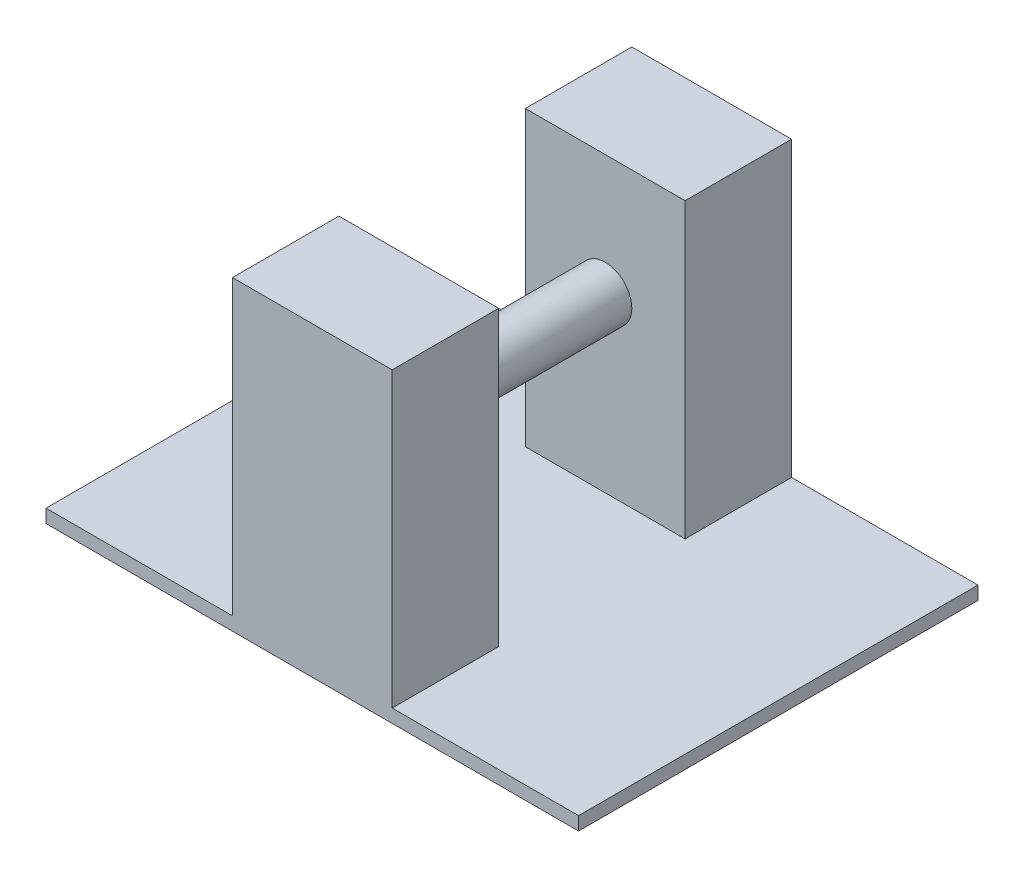
SolidWorks part; units mm, degrees
ref_plane "Front Plane" through (0, 0, 0) normal (0, 0, 1) x (1, 0, 0)
ref_plane "Top Plane" through (0, 0, 0) normal (0, 1, 0) x (1, 0, 0)
ref_plane "Right Plane" through (0, 0, 0) normal (1, 0, 0) x (0, 0, -1)
sketch "Sketch2" plane through (0, 0, 0) normal (0, 1, 0) x (1, 0, 0)
  line L1 (-127, -95.25) -> (127, -95.25)
  line L2 (-127, -95.25) -> (-127, 95.25)
  line L3 (-127, 95.25) -> (127, 95.25)
  line L4 (127, -95.25) -> (127, 95.25)
  line L5 (-127, -95.25) -> (127, 95.25) construction
  line L6 (-127, 95.25) -> (127, -95.25) construction
  point P0 (0, 0)
  dimension "D1" = 190.5
  dimension "D2" = 254
extrude "Boss-Extrude2" add sketch "Sketch2" along normal blind 6.35
sketch "Sketch4" plane through (0, 6.35, 0) normal (0, 1, 0) x (1, 0, 0)
  line L0 (-127, -95.25) -> (0, -95.25) construction
  line L1 (-127, -95.25) -> (127, -95.25) construction
  line L2 (0, -95.25) -> (0, -69.85) construction
  line L3 (0, -69.85) -> (38.1, -69.85) construction
  line L4 (38.1, -69.85) -> (38.1, -44.45) construction
  line L6 (-38.1, -95.25) -> (38.1, -95.25)
  line L7 (-38.1, -95.25) -> (-38.1, -44.45)
  line L8 (-38.1, -44.45) -> (38.1, -44.45)
  line L9 (38.1, -95.25) -> (38.1, -44.45)
  line L10 (-38.1, -95.25) -> (38.1, -44.45) construction
  line L11 (-38.1, -44.45) -> (38.1, -95.25) construction
  dimension "D1" = 25.4
  dimension "D2" = 38.1
  dimension "D3" = 25.4
extrude "Boss-Extrude3" add sketch "Sketch4" along normal blind 139.7
mirror "Mirror1" about plane through (0, 0, 0) normal (0, 0, 1) of "Boss-Extrude3"
sketch "Sketch11" plane through (0, 0, 95.25) normal (0, 0, 1) x (1, 0, 0)
  line L0 (0, 0) -> (0, 88.9) construction
  line L2 (-127, 0) -> (127, 0) construction
  circle A1 centre (0, 88.9) radius 12.7
  dimension "D2" = 25.4
  dimension "D1" = 88.9
extrude "Boss-Extrude4" add sketch "Sketch11" against normal up to surface (139.7 mm away) up to face at (0, 76.2, -44.45)
